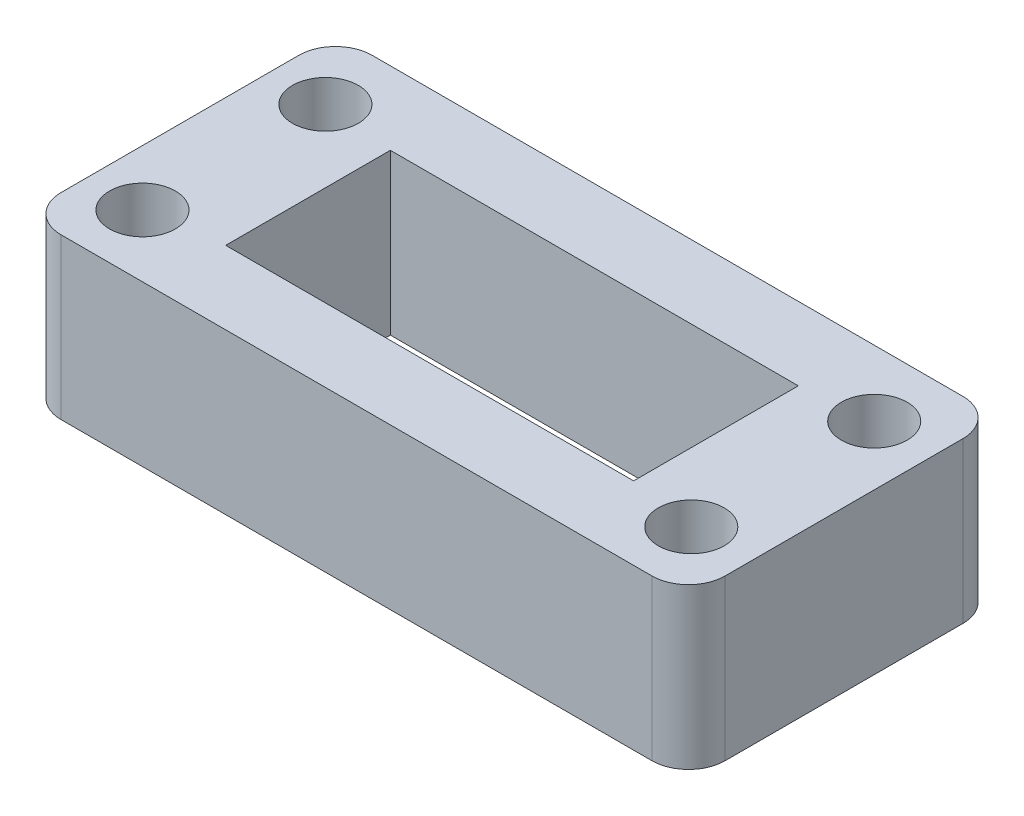
SolidWorks part; units mm, degrees
ref_plane "Front Plane" through (0, 0, 0) normal (0, 0, 1) x (1, 0, 0)
ref_plane "Top Plane" through (0, 0, 0) normal (0, 1, 0) x (1, 0, 0)
ref_plane "Right Plane" through (0, 0, 0) normal (1, 0, 0) x (0, 0, -1)
sketch "Sketch1" plane through (0, 0, 0) normal (0, 1, 0) x (1, 0, 0)
  line L0 (0, 0) -> (36.3, 0)
  line L1 (36.3, 0) -> (36.3, 17)
  line L2 (36.3, 17) -> (0, 17)
  line L3 (0, 17) -> (0, 0)
  line L4 (7, 13) -> (7, 4)
  line L5 (7, 4) -> (29.3, 4)
  line L6 (29.3, 4) -> (29.3, 13)
  line L7 (29.3, 13) -> (7, 13)
  line L8 (0, 8.5) -> (36.3, 8.5) construction
  line L9 (18.15, 0) -> (18.15, 17) construction
  point P13 (18.15, 13)
  point P14 (29.3, 8.5)
  dimension "D1" = 7
  dimension "D2" = 4
  dimension "D3" = 36.3
  dimension "D4" = 17
extrude "Boss-Extrude1" add sketch "Sketch1" along normal blind 8.75
sketch "Sketch2" plane through (0, 8.75, 0) normal (0, 1, 0) x (1, 0, 0)
  point P0 (3.05, 3.4)
  point P6 (33.05, 3.4)
  point P9 (33.05, 13.4)
  point P15 (3.05, 13.4)
hole_wizard "M3 Clearance Hole1" positions "Sketch2" profile "Sketch3" hole size "M3" standard "ANSI Metric" end condition through all
sketch "Sketch3" plane through (3.05, 8.75, -3.4) normal (1, 0, 0) x (0, 0, 1)
  line L0 (0, 0) -> (0, 8.75)
  line L1 (0, 8.75) -> (1.8, 8.75)
  line L2 (1.8, 8.75) -> (1.8, 0)
  line L5 (1.8, 0) -> (0, 0)
  line L11 (0, -6.35) -> (0, 107.95) construction
  dimension "Thru Hole Dia." = 3.6
  dimension "Thru Hole Depth" = 8.75
fillet "Fillet1" radius 2 4 edges at (0, 4.375, -17) (36.3, 4.375, -17) (36.3, 4.375, 0) (0, 4.375, 0)
